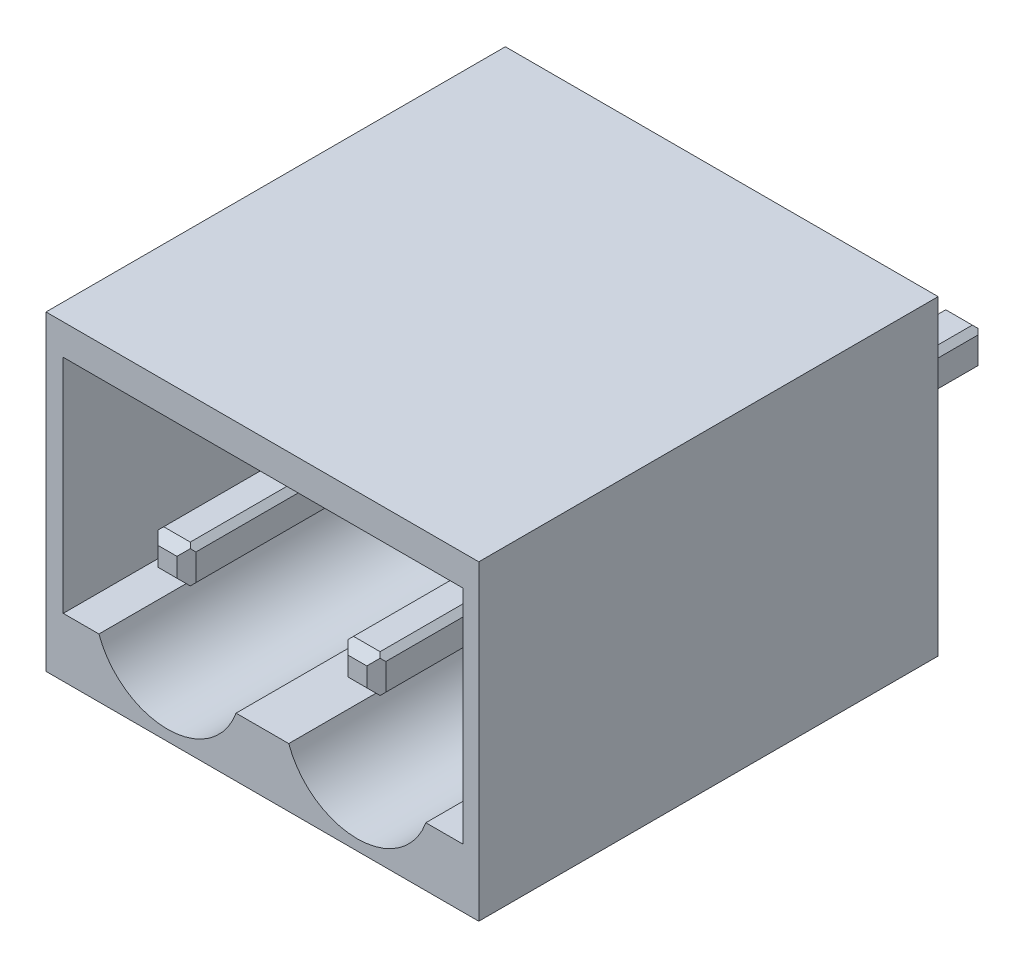
SolidWorks part; units mm, degrees
ref_plane "Спереди" through (0, 0, 0) normal (0, 0, 1) x (1, 0, 0)
ref_plane "Сверху" through (0, 0, 0) normal (0, 1, 0) x (1, 0, 0)
ref_plane "Справа" through (0, 0, 0) normal (1, 0, 0) x (0, 0, -1)
sketch "Эскиз1" plane through (0, 0, 0) normal (0, 0, 1) x (1, 0, 0)
  line L1 (-5.7, 4.1) -> (5.7, 4.1)
  line L2 (-5.7, 4.1) -> (-5.7, -4.1)
  line L3 (-5.7, -4.1) -> (5.7, -4.1)
  line L4 (5.7, 4.1) -> (5.7, -4.1)
  line L5 (-5.7, 4.1) -> (5.7, -4.1) construction
  line L6 (-5.7, -4.1) -> (5.7, 4.1) construction
  point P0 (0, 0)
  dimension "D1" = 8.2
  dimension "D2" = 11.4
extrude "Бобышка-Вытянуть1" add sketch "Эскиз1" along normal blind 12.1
sketch "Эскиз4" plane through (0, 0, 12.1) normal (0, 0, 1) x (1, 0, 0)
  circle A0 centre (-2.5, 0) radius 1.25
  circle A1 centre (2.5, 0) radius 1.25
  dimension "D1" = 2.5
  dimension "D2" = 2.5
  dimension "D3" = 2
extrude "Вырез-Вытянуть3" cut sketch "Эскиз4" against normal blind 8
sketch "Эскиз5" plane through (0, 0, 12.1) normal (0, 0, 1) x (1, 0, 0)
  line L0 (-5.2456, 0) -> (-5.2456, 3.2929)
  line L1 (-5.2456, 3.2929) -> (5.2785, 3.2929)
  line L2 (5.2785, 3.2929) -> (5.2785, -2.549)
  line L4 (-5.2456, -2.549) -> (-5.2456, 0)
  line L6 (-4.3058, -2.549) -> (-5.2456, -2.549)
  line L7 (-0.6942, -2.549) -> (0.6942, -2.549)
  line L8 (4.3058, -2.549) -> (5.2785, -2.549)
  arc A5 (-4.3058, -2.549) -> (-0.6942, -2.549) centre (-2.5, -1.9) ccw
  arc A6 (0.6942, -2.549) -> (4.3058, -2.549) centre (2.5, -1.9) ccw
  dimension "D1" = 3.2
  dimension "D2" = 2.2
  dimension "D3" = 2
extrude "Вырез-Вытянуть4" cut sketch "Эскиз5" against normal blind 7.8
sketch "Эскиз7" plane through (0, 0, 4.1) normal (0, 0, 1) x (1, 0, 0)
  line L0 (2, 0.5) -> (3, 0.5)
  line L1 (-3, 0.5) -> (-2, 0.5)
  line L2 (-3, 0.5) -> (-3, -0.5)
  line L3 (-3, -0.5) -> (-2, -0.5)
  line L4 (-2, 0.5) -> (-2, -0.5)
  line L5 (-3, 0.5) -> (-2, -0.5) construction
  line L6 (-3, -0.5) -> (-2, 0.5) construction
  line L7 (2, 0.5) -> (2, -0.5)
  line L8 (2, -0.5) -> (3, -0.5)
  line L9 (3, 0.5) -> (3, -0.5)
  line L10 (2, 0.5) -> (3, -0.5) construction
  line L11 (2, -0.5) -> (3, 0.5) construction
  point P0 (-2.5, 0)
  point P7 (2.5, 0)
  dimension "D1" = 1
  dimension "D2" = 1
  dimension "D3" = 2
extrude "Бобышка-Вытянуть2" add sketch "Эскиз7" along normal blind 8
chamfer "Фаска1" distance 0.15 angle 45 8 edges at (2, -0.5, 8.1) (2, 0.5, 8.1) (3, 0.5, 8.1) (3, -0.5, 8.1) (-2, -0.5, 8.1) (-2, 0.5, 8.1) (-3, -0.5, 8.1) (-3, 0.5, 8.1)
chamfer "Фаска2" distance 0.25 angle 45 8 edges at (2, 0, 12.1) (2.5, 0.5, 12.1) (3, 0, 12.1) (2.5, -0.5, 12.1) (-2, 0, 12.1) (-2.5, -0.5, 12.1) (-3, 0, 12.1) (-2.5, 0.5, 12.1)
sketch "Эскиз9" plane through (0, 0, 0) normal (0, 0, -1) x (-1, 0, 0)
  line L0 (2, 0.15) -> (3, 0.15)
  line L1 (-3, 0.15) -> (-2, 0.15)
  line L2 (-3, 0.15) -> (-3, -0.85)
  line L3 (-3, -0.85) -> (-2, -0.85)
  line L4 (-2, 0.15) -> (-2, -0.85)
  line L5 (-3, 0.15) -> (-2, -0.85) construction
  line L6 (-3, -0.85) -> (-2, 0.15) construction
  line L7 (2, 0.15) -> (2, -0.85)
  line L8 (2, -0.85) -> (3, -0.85)
  line L9 (3, 0.15) -> (3, -0.85)
  line L10 (2, 0.15) -> (3, -0.85) construction
  line L11 (2, -0.85) -> (3, 0.15) construction
  point P0 (-2.5, -0.35)
  point P7 (2.5, -0.35)
  dimension "D1" = 1
  dimension "D2" = 1
  dimension "D3" = 3.2
  dimension "D4" = 4.45
  dimension "D5" = 2
extrude "Бобышка-Вытянуть4" add sketch "Эскиз9" along normal blind 4
chamfer "Фаска5" distance 0.15 angle 45 8 edges at (3, -0.85, -2) (-2, -0.85, -2) (-3, -0.85, -2) (2, -0.85, -2) (3, 0.15, -2) (-2, 0.15, -2) (-3, 0.15, -2) (2, 0.15, -2)
chamfer "Фаска6" distance 0.25 angle 45 8 edges at (-2.5, -0.85, -4) (2.5, -0.85, -4) (3, -0.35, -4) (2, -0.35, -4) (-2, -0.35, -4) (-3, -0.35, -4) (-2.5, 0.15, -4) (2.5, 0.15, -4)
